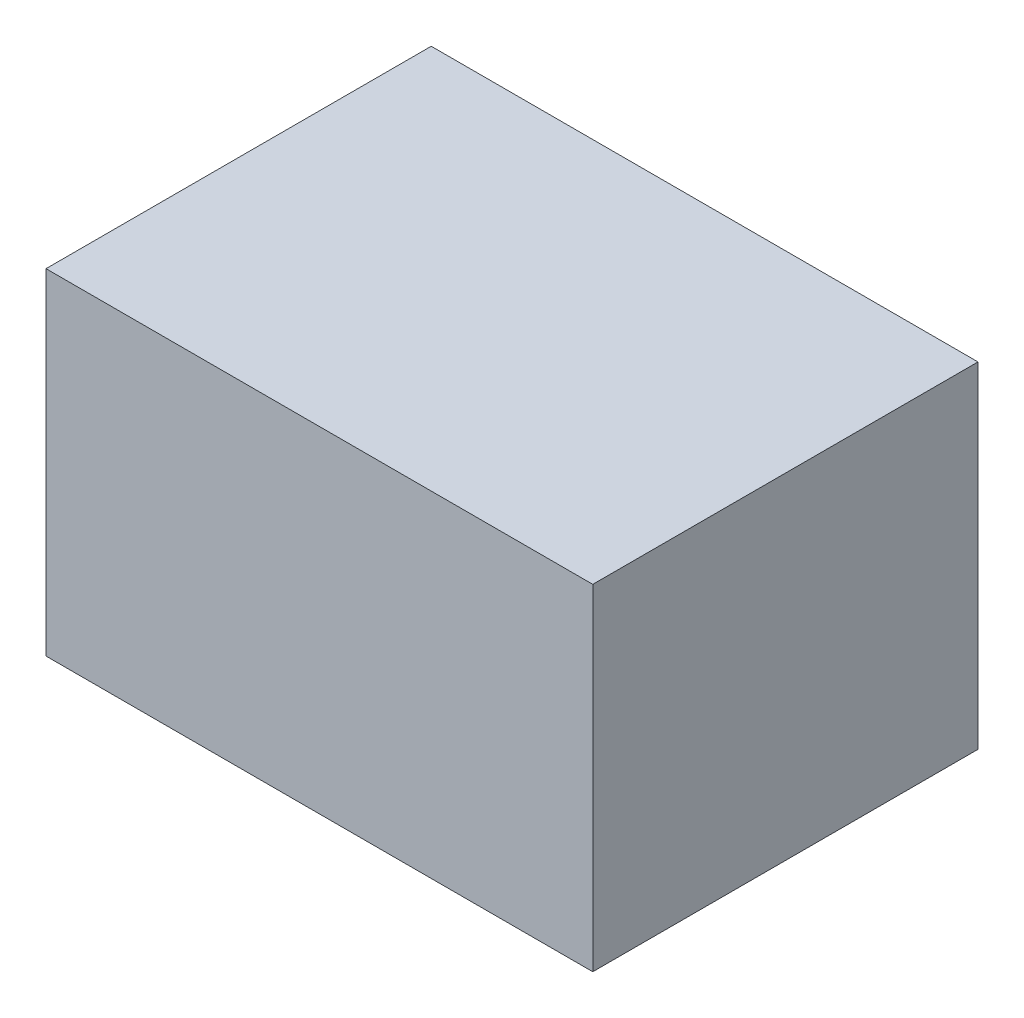
SolidWorks part; units mm, degrees
ref_plane "Front Plane" through (0, 0, 0) normal (0, 0, 1) x (1, 0, 0)
ref_plane "Top Plane" through (0, 0, 0) normal (0, 1, 0) x (1, 0, 0)
ref_plane "Right Plane" through (0, 0, 0) normal (1, 0, 0) x (0, 0, -1)
sketch "Sketch1" plane through (0, 0, 0) normal (0, 0, 1) x (1, 0, 0)
  line L1 (-11, -6.75) -> (11, -6.75)
  line L2 (-11, -6.75) -> (-11, 6.75)
  line L3 (-11, 6.75) -> (11, 6.75)
  line L4 (11, -6.75) -> (11, 6.75)
  line L5 (-11, -6.75) -> (11, 6.75) construction
  line L6 (-11, 6.75) -> (11, -6.75) construction
extrude "Envelope" add sketch "Sketch1" along normal blind 15.5
